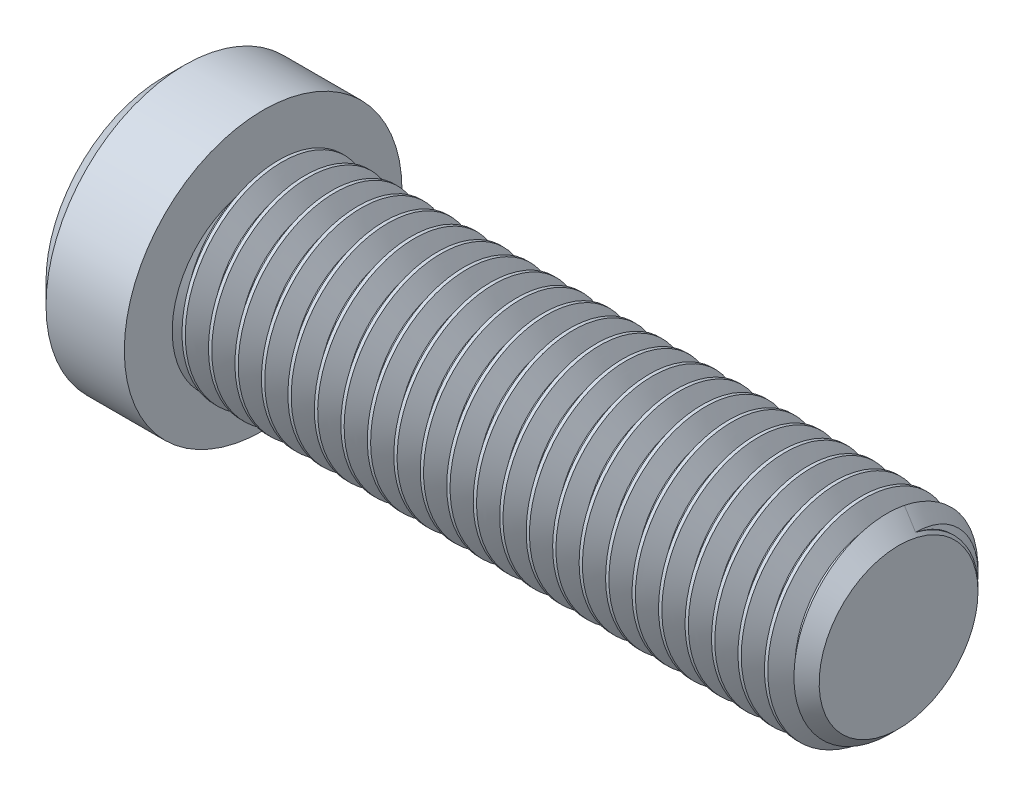
SolidWorks part; units mm, degrees
ref_plane "Front Plane" through (0, 0, 0) normal (0, 0, 1) x (1, 0, 0)
ref_plane "Top Plane" through (0, 0, 0) normal (0, 1, 0) x (1, 0, 0)
ref_plane "Right Plane" through (0, 0, 0) normal (1, 0, 0) x (0, 0, -1)
sketch "Sketch1" plane through (0, 0, 0) normal (0, 0, 1) x (1, 0, 0)
  line L0 (12.7, 0) -> (-12.7, 0) construction
  line L1 (12.7, 3.9688) -> (12.7, -3.9687) construction
  line L2 (-12.7, 5.5499) -> (-12.7, -5.5499) construction
  line L3 (-12.7, 5.5499) -> (-15.8305, 5.5499) construction
  line L4 (-15.8305, 5.5499) -> (-16.6687, 4.7117) construction
  line L5 (-16.6687, 4.7117) -> (-16.6687, -4.7117) construction
  line L6 (-16.6687, -4.7117) -> (-15.8305, -5.5499) construction
  line L7 (-15.8305, -5.5499) -> (-12.7, -5.5499) construction
  point P7 (-13.8748, 0)
  point P12 (8.4667, -3.9687)
  dimension "D1" = 45
  dimension "Dec." = 7.9375
  dimension "Length" = 25.4
  dimension "Head Dia" = 11.0998
  dimension "Head Height" = 3.9688
  dimension "Hex Depth" = 2.794
  dimension "Chamfer" = 0.8382
  dimension "D2" = 4.2333
ref_plane "Plane1" through (12.7, 0, 0) normal (1, 0, 0) x (0, 0, -1)
ref_plane "Plane2" through (-16.6687, 0, 0) normal (1, 0, 0) x (0, 0, -1)
sketch "Sketch2" plane through (12.7, 0, 0) normal (1, 0, 0) x (0, 0, -1)
  circle A0 centre (0, 0) radius 3.9687
extrude "Boss-Extrude1" add sketch "Sketch2" against normal up to vertex (25.4 mm away) up to point (-12.7, 0, 0)
sketch "Sketch3" plane through (12.7, 0, 0) normal (1, 0, 0) x (0, 0, -1)
  circle A0 centre (0, 0) radius 3.9687 construction
  circle A1 centre (0, 0) radius 3.9687
curve "Helix/Spiral1" pitch 1.0583 height 26.4583 radius 3.9687 centre (12.7, 0, 0) axis (-1, 0, 0) start towards (0, 1, 0) parameters "Pitch"=1.0583
chamfer "Chamfer1" distance 0.7937 angle 45 1 edges at (12.7, 0, -3.9687)
sketch "Sketch5" plane through (0, 0, 0) normal (0, 0, 1) x (1, 0, 0)
  line L0 (12.237, 3.9688) -> (13.163, 3.9688)
  line L1 (13.163, 3.9688) -> (12.7661, 3.2813)
  line L2 (12.7661, 3.2813) -> (12.6339, 3.2813)
  line L3 (12.6339, 3.2813) -> (12.237, 3.9688)
  line L4 (12.7, 3.2813) -> (12.7, 3.9688) construction
  line L5 (12.4354, 3.625) -> (12.9646, 3.625) construction
  dimension "D1" = 60
  dimension "D2" = 0.5292
  dimension "D3" = 0.1323
sweep "Cut-Sweep1" cut profiles "Sketch5" path "Helix/Spiral1" align with end faces yes
sketch "Sketch4" plane through (-16.6687, 0, 0) normal (1, 0, 0) x (0, 0, -1)
  line L0 (-5.5499, 0.7937) -> (5.5499, 0.7937) construction
  line L1 (0, 2.2914) -> (-1.9844, 1.1457)
  line L2 (-1.9844, 1.1457) -> (-1.9844, -1.1457)
  line L3 (-1.9844, -1.1457) -> (0, -2.2914)
  line L4 (0, -2.2914) -> (1.9844, -1.1457)
  line L5 (1.9844, -1.1457) -> (1.9844, 1.1457)
  line L6 (1.9844, 1.1457) -> (0, 2.2914)
  line L7 (0, 0) -> (0, 0.7937) construction
  circle A0 centre (0, 0) radius 1.9844 construction
  dimension "Hex Size" = 3.9688
  dimension "D1" = 11.0998
  dimension "D2" = 0.7937
sketch "Sketch6" plane through (0, 0, 0) normal (0, 0, 1) x (1, 0, 0)
  line L0 (-15.8305, 5.5499) -> (-16.6687, 4.7117) construction
  line L1 (-12.7, 5.5499) -> (-15.8305, 5.5499) construction
  line L2 (-12.7, 5.5499) -> (-12.7, -5.5499) construction
  line L3 (-16.6687, 4.7117) -> (-16.6687, -4.7117) construction
  line L4 (-15.8305, 5.5499) -> (-16.6687, 4.7117)
  line L5 (-12.7, 5.5499) -> (-15.8305, 5.5499)
  line L6 (-12.7, 5.5499) -> (-12.7, 0)
  line L7 (-16.6687, 4.7117) -> (-16.6687, 0)
  line L8 (-12.7, 0) -> (-16.6687, 0) construction
  line L9 (-12.7, 0) -> (-16.6687, 0)
revolve "Revolve1" add sketch "Sketch6" angle 360 about L8
extrude "Cut-Extrude1" cut sketch "Sketch4" along normal up to vertex (2.794 mm away) up to point (-13.8748, 0, 0)
sketch "Sketch8" plane through (-16.6688, 0, 0) normal (-1, 0, 0) x (0, 0, 1)
  circle A1 centre (0, 0) radius 2.2914
extrude "Cut-Extrude2" cut sketch "Sketch8" against normal through all draft 45
equation "\"D3@Helix/Spiral1\" = \"Length@Sketch1\"+\"Pitch@Helix/Spiral1\""
equation "\"D3@Sketch5\" = \"Pitch@Helix/Spiral1\"*.125"
equation "\"D2@Sketch5\" = \"Pitch@Helix/Spiral1\"*.50"
equation "\"D1@Chamfer1\" = \"Pitch@Helix/Spiral1\"*.75"
equation "\"D2@Sketch1\" = \"Pitch@Helix/Spiral1\"*4"
equation "\"D1@Sketch4\" = \"Head Dia@Sketch1\""
